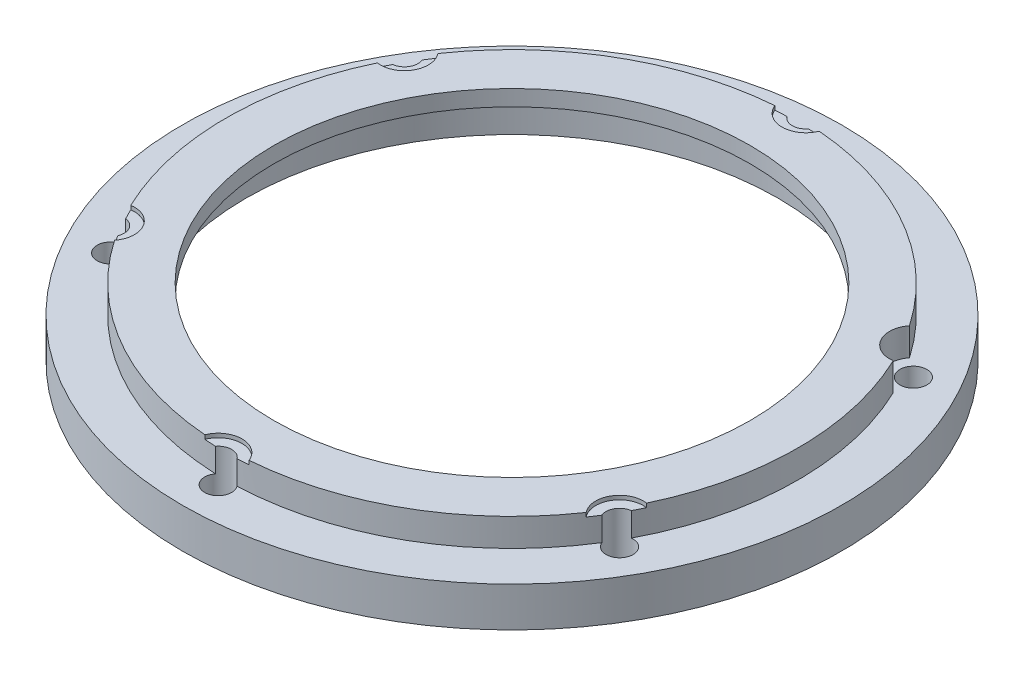
SolidWorks part; units mm, degrees
ref_plane "前视基准面" through (0, 0, 0) normal (0, 0, 1) x (1, 0, 0)
ref_plane "上视基准面" through (0, 0, 0) normal (0, 1, 0) x (1, 0, 0)
ref_plane "右视基准面" through (0, 0, 0) normal (1, 0, 0) x (0, 0, -1)
sketch "草图2" plane through (0, 0, 0) normal (1, 0, 0) x (0, 0, -1)
  line L9 (-30, 0) -> (-30, 2)
  line L10 (-30, 2) -> (-36, 2)
  line L11 (-30, 0) -> (-33.5, 0)
  line L12 (-33.5, 0) -> (-33.5, -5.5)
  line L13 (-33.5, -5.5) -> (-35, -5.5)
  line L14 (-35, -5.5) -> (-35, -6.5)
  line L15 (-35, -6.5) -> (-41.5, -6.5)
  line L16 (-36, 2) -> (-36, -1.5)
  line L17 (-36, -1.5) -> (-41.5, -1.5)
  line L18 (-41.5, -1.5) -> (-41.5, -6.5)
ref_axis "基准轴1" through (0, 0, 0) along (0, 1, 0)
revolve "旋转1" add sketch "草图2" angle 360 about axis through (0, 0, 0) along (0, 1, 0)
sketch "草图3" plane through (0, -1.5, 0) normal (0, 1, 0) x (1, 0, 0)
  circle A0 centre (0, 37) radius 1.7
  circle A1 centre (32.0429, 18.5) radius 1.7
  circle A2 centre (32.0429, -18.5) radius 1.7
  circle A3 centre (0, -37) radius 1.7
  circle A4 centre (-32.0429, -18.5) radius 1.7
  circle A5 centre (-32.0429, 18.5) radius 1.7
  point P16 (0, 0)
  dimension "D1" = 6
extrude "切除-拉伸1" cut sketch "草图3" against normal blind 10 and the other way up to next
sketch "草图4" plane through (0, -1.5, 0) normal (0, 1, 0) x (1, 0, 0)
  circle A0 centre (0, 37) radius 3
  circle A1 centre (32.0429, 18.5) radius 3
  circle A2 centre (32.0429, -18.5) radius 3
  circle A3 centre (0, -37) radius 3
  circle A4 centre (-32.0429, -18.5) radius 3
  circle A5 centre (-32.0429, 18.5) radius 3
  point P16 (0, 0)
  dimension "D1" = 6
extrude "切除-拉伸2" cut sketch "草图4" along normal blind 3 from offset 3
sketch "草图7" plane through (0, -1.5, 0) normal (0, 1, 0) x (1, 0, 0)
  circle A0 centre (32.0429, 18.5) radius 3
extrude "切除-拉伸3" cut sketch "草图7" along normal blind 10
